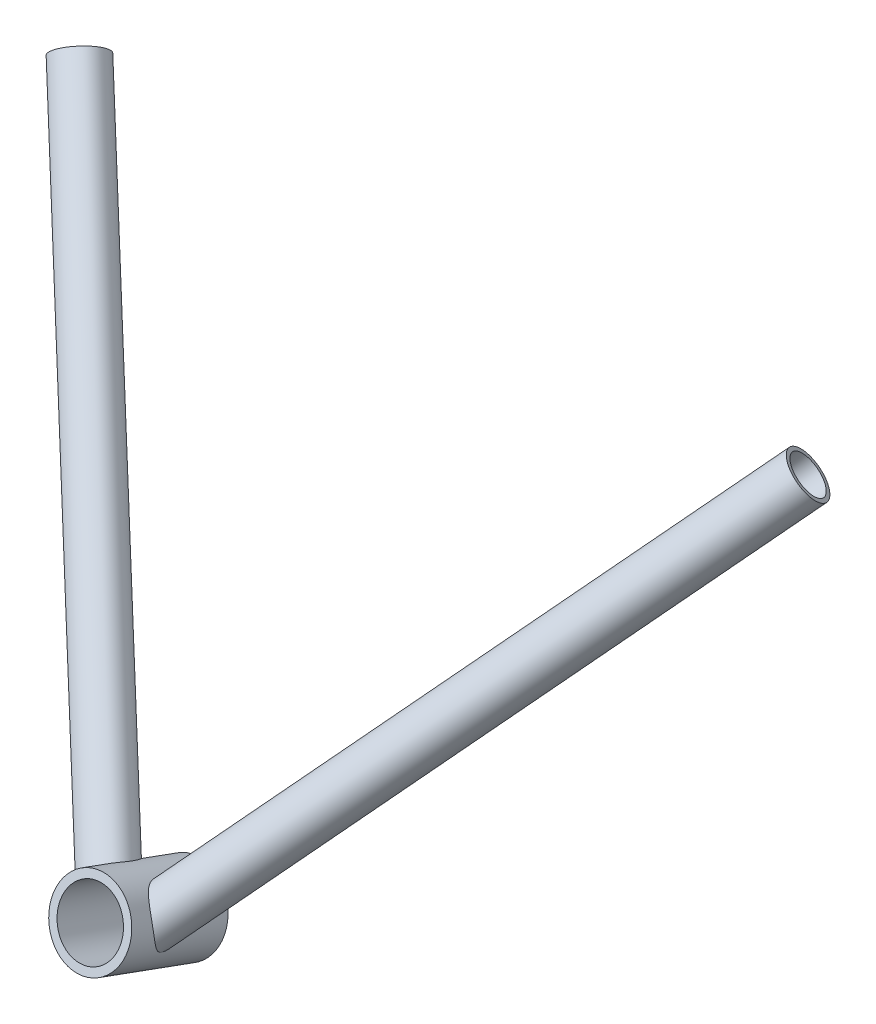
SolidWorks part; units mm, degrees
material "AISI 4130 Steel, normalized at 870C"
ref_plane "Front Plane" through (0, 0, 0) normal (0, 0, 1) x (1, 0, 0)
ref_plane "Top Plane" through (0, 0, 0) normal (0, 1, 0) x (1, 0, 0)
ref_plane "Right Plane" through (0, 0, 0) normal (1, 0, 0) x (0, 0, -1)
sketch "Sketch3" plane through (0, 0, 0) normal (0, 1, 0) x (1, 0, 0)
  line L0 (-5.08, -6.35) -> (5.08, -6.35) construction
  line L2 (0, -88.2205) -> (0, 88.2205) construction
  line L3 (5.08, 0) -> (-5.08, 0) construction
  dimension "D1" = 5.08
  dimension "D2" = 10.16
  dimension "D3" = 6.35
  dimension "D4" = 10.16
  dimension "D5" = 5.08
ref_plane "Plane1" through (0, 3.0807, 3.9431) normal (0, 0.6157, 0.788) x (1, 0, 0)
ref_plane "Plane3" through (0, 0, 0) normal (0, 0.342, 0.9397) x (-1, 0, 0)
sketch "Sketch1" plane through (0, 0, 0) normal (0, 0.342, 0.9397) x (1, 0, 0)
  circle A0 centre (0, 0) radius 15.875
  dimension "D1" = 31.75
extrude "Boss-Extrude1" add sketch "Sketch1" along normal mid plane 41.402 contours A0
sketch "Sketch4" plane through (0, 3.0807, 3.9431) normal (0, 0.6157, 0.788) x (1, 0, 0)
  line L0 (-5.08, -3.9095) -> (-147.115, 206.6661)
  line L2 (0, -89.5666) -> (0, 89.5666) construction
  dimension "D2" = 34
  dimension "D3" = 254
sweep "Sweep1" add path "Sketch4" circular profile diameter 19.05 parameters "D3"=19.05
sketch "Sketch15" plane through (0, 3.0807, 3.9431) normal (0, 0.6157, 0.788) x (1, 0, 0)
  line L0 (5.08, -3.9095) -> (147.115, 206.6661)
  line L1 (0, -89.5666) -> (0, 89.5666) construction
  dimension "D1" = 254
  dimension "D2" = 34
sweep "Sweep2" add path "Sketch15" circular profile diameter 19.05 parameters "D3"=19.05
sketch "Sketch36" plane through (-141.8111, 165.6742, -129.4389) normal (-0.5592, 0.6533, -0.5104) x (0.8289, 0.4282, -0.36)
  circle A0 centre (-6.4965, -4.8749) radius 7.9375
  dimension "D1" = 15.875
extrude "Cut-Extrude2" cut sketch "Sketch36" against normal up to surface (263.9627 mm away) up to face at (15.3187, -2.4813, 5.3626)
sketch "Sketch37" plane through (141.8111, 165.6742, -129.4389) normal (0.5592, 0.6533, -0.5104) x (0.8289, -0.4282, 0.36)
  circle A0 centre (6.4965, -4.8749) radius 7.9375
  dimension "D1" = 15.875
extrude "Cut-Extrude3" cut sketch "Sketch37" against normal up to surface (239.4455 mm away) up to face at (10.3406, -6.3305, 17.8251)
sketch "Sketch77" plane through (0, 7.0802, 19.4526) normal (0, 0.342, 0.9397) x (1, 0, 0)
  circle A1 centre (0, 0) radius 15.875
extrude "Boss-Extrude2" add sketch "Sketch77" against normal up to surface (41.402 mm away) up to face at (0, -21.9978, -14.023)
sketch "Sketch2" plane through (0, -7.0802, -19.4526) normal (0, -0.342, -0.9397) x (-1, 0, 0)
  circle A0 centre (0, 0) radius 12.7
  dimension "D1" = 25.4
extrude "Cut-Extrude1" cut sketch "Sketch2" against normal up to next
ref_plane "Plane2" through (0, 0, -127) normal (0, 0, 1) x (1, 0, 0)
sketch "Sketch40" plane through (-106.934, 0, -127) normal (0, 0, 1) x (1, 0, 0)
  line L2 (106.934, -90.5202) -> (106.934, 90.5202) construction
  line L3 (94.4829, 187.4611) -> (-59.7307, 169.3775)
  line L4 (119.3851, 187.4611) -> (273.5987, 169.3775)
  arc A0 (94.4829, 187.4611) -> (119.3851, 187.4611) centre (106.934, 81.28) cw
  point P0 (106.934, 188.1886)
  point P7 (106.934, 188.1886)
  dimension "D1" = 155.2702
  dimension "D3" = 106.9086
  dimension "D2" = 155.2702
  dimension "D4" = 7.6
  dimension "D5" = 106.9086
sweep "Sweep3" [suppressed] add path "Sketch40" circular profile diameter 25.4 parameters "D3"=25.4
